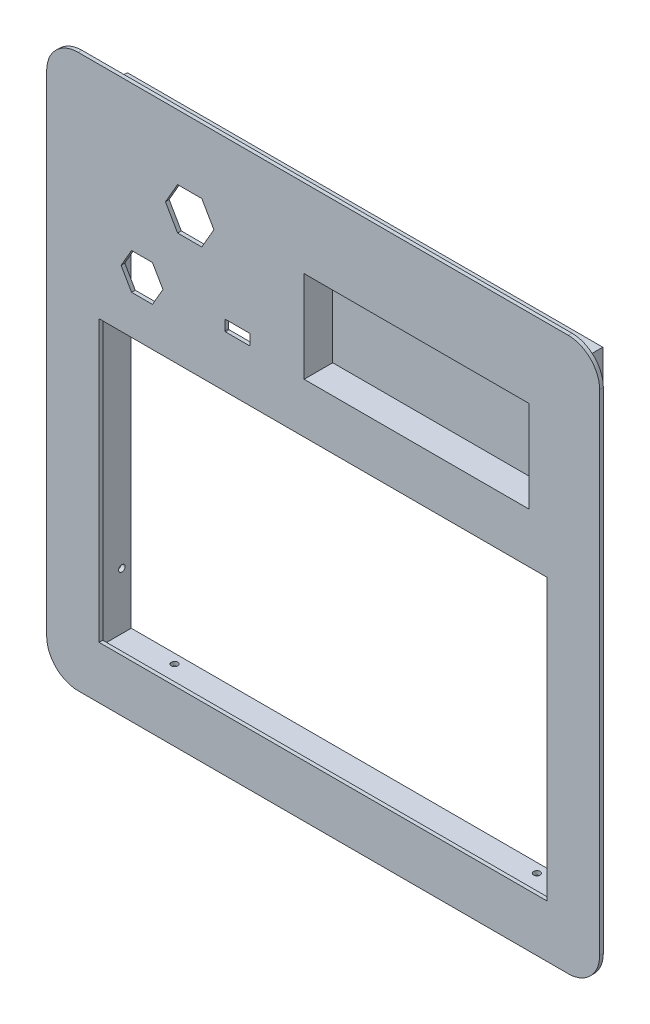
SolidWorks part; units mm, degrees
ref_plane "Front Plane" through (0, 0, 0) normal (0, 0, 1) x (1, 0, 0)
ref_plane "Top Plane" through (0, 0, 0) normal (0, 1, 0) x (1, 0, 0)
ref_plane "Right Plane" through (0, 0, 0) normal (1, 0, 0) x (0, 0, -1)
sketch "Sketch3" plane through (0, 0, 0) normal (0, 0, 1) x (1, 0, 0)
  line L0 (-117.5, 29.5) -> (117.5, 29.5)
  line L1 (-117.5, 29.5) -> (-117.5, -117.5)
  line L2 (-117.5, -117.5) -> (117.5, -117.5)
  line L3 (117.5, 29.5) -> (117.5, -117.5)
  line L8 (-38.77, 62.35) -> (-51.23, 62.35)
  line L9 (-51.54, 62.04) -> (-51.54, 56.96)
  line L10 (-51.23, 56.65) -> (-38.77, 56.65)
  line L11 (-38.46, 56.96) -> (-38.46, 62.04)
  line L12 (-12, 105.75) -> (110, 105.75)
  line L13 (-128.49, -145) -> (128.49, -145)
  line L14 (-145, -128.49) -> (-145, 128.49)
  line L15 (-128.49, 145) -> (128.49, 145)
  line L16 (145, -128.49) -> (145, 128.49)
  line L29 (-12, 105.75) -> (-12, 53.75)
  line L30 (-12, 53.75) -> (110, 53.75)
  line L31 (110, 105.75) -> (110, 53.75)
  line L32 (-70, 100) -> (-70, 59.5) construction
  line L33 (-57.2983, 100) -> (-63.6491, 111)
  line L34 (-84.0303, 59.5) -> (-89.5152, 69)
  line L35 (-89.5152, 69) -> (-100.4848, 69)
  line L36 (-100.4848, 69) -> (-105.9697, 59.5)
  line L37 (-105.9697, 59.5) -> (-100.4848, 50)
  line L38 (-100.4848, 50) -> (-89.5152, 50)
  line L39 (-89.5152, 50) -> (-84.0303, 59.5)
  line L40 (-63.6491, 111) -> (-76.3509, 111)
  line L41 (-76.3509, 111) -> (-82.7017, 100)
  line L42 (-82.7017, 100) -> (-76.3509, 89)
  line L43 (-76.3509, 89) -> (-63.6491, 89)
  line L44 (-63.6491, 89) -> (-57.2983, 100)
  arc A0 (-38.77, 56.65) -> (-38.46, 56.96) centre (-38.77, 56.96) ccw
  arc A1 (-51.54, 56.96) -> (-51.23, 56.65) centre (-51.23, 56.96) ccw
  arc A2 (-38.77, 62.35) -> (-38.46, 62.04) centre (-38.77, 62.04) cw
  arc A3 (-51.23, 62.35) -> (-51.54, 62.04) centre (-51.23, 62.04) ccw
  arc A4 (128.49, -145) -> (145, -128.49) centre (128.49, -128.49) ccw
  arc A5 (-128.49, -145) -> (-145, -128.49) centre (-128.49, -128.49) cw
  arc A6 (128.49, 145) -> (145, 128.49) centre (128.49, 128.49) cw
  arc A7 (-145, 128.49) -> (-128.49, 145) centre (-128.49, 128.49) cw
  circle A10 centre (-95, 59.5) radius 9.5 construction
  circle A11 centre (-70, 100) radius 11 construction
  point P26 (-51.54, 59.5)
  point P30 (-70, 79.75)
  point P32 (-45, 62.35)
  point P44 (-12, 79.75)
  point P58 (145, 0)
  point P59 (0, 145)
  dimension "D5" = 0.31
  dimension "D6" = 16.51
  dimension "D10" = 22
  dimension "D25" = 19
  dimension "D7" = 25
  dimension "D1" = 235
  dimension "D2" = 147
  dimension "D3" = 12.46
  dimension "D4" = 5.08
  dimension "D8" = 27.5
  dimension "D9" = 27.5
  dimension "D11" = 45
  dimension "D12" = 50
  dimension "D13" = 25
  dimension "D17" = 122
  dimension "D18" = 52
  dimension "D20" = 35
  dimension "D21" = 290
  dimension "D22" = 290
  dimension "D26" = 30
extrude "Boss-Extrude1" add sketch "Sketch3" against normal blind 2 draft 2 contours L31 L12 L29 L30 | A7 L14 A5 L13 A4 L16 A6 L15 A3 L8 A2 L11 A0 L10 A1 L9 L44 L43 L42 L41 L40 L33 L39 L38 L37 L36 L35 L34 L0 L3 L2 L1 L12 L31 L30 L29 region at (49, 79.75, 0) region at (-137.2643, -137.2643, 0)
ref_plane "Plane1" through (0, 0, -22) normal (0, 0, -1) x (-1, 0, 0)
sketch "Sketch4" plane through (0, 0, -22) normal (0, 0, -1) x (-1, 0, 0)
  line L1 (-124.65, -126.65) -> (124.65, -126.65)
  line L2 (-124.65, -126.65) -> (-124.65, 126.65)
  line L3 (-124.65, 126.65) -> (124.65, 126.65)
  line L4 (124.65, -126.65) -> (124.65, 126.65)
  line L5 (-124.65, -126.65) -> (124.65, 126.65) construction
  line L6 (-124.65, 126.65) -> (124.65, -126.65) construction
  point P0 (0, 0)
  dimension "D1" = 249.3
  dimension "D2" = 253.3
extrude "Boss-Extrude2" add sketch "Sketch4" against normal blind 20 draft 2 draft outward yes
sketch "Sketch5" plane through (0, 0, -22) normal (0, 0, -1) x (-1, 0, 0)
  line L14 (-122.65, -124.65) -> (122.65, -124.65)
  line L15 (122.65, -124.65) -> (122.65, 124.65)
  line L16 (-122.65, 124.65) -> (-122.65, -124.65)
  line L17 (122.65, 124.65) -> (-122.65, 124.65)
  line L18 (-122.65, -124.65) -> (122.65, -124.65)
  line L19 (122.65, -124.65) -> (122.65, 124.65)
  line L20 (-122.65, 124.65) -> (-122.65, -124.65)
  line L21 (122.65, 124.65) -> (-122.65, 124.65)
  dimension "D1" = 2
extrude "Cut-Extrude1" cut sketch "Sketch5" against normal blind 20
extrude "Boss-Extrude3" add sketch "Sketch3<3>" against normal blind 17 contours L31 L12 L29 L30 region at (49, 79.75, 0)
sketch "Sketch3<3>" plane through (0, 0, 0) normal (0, 0, 1) x (1, 0, 0) same geometry as "Sketch3"
sketch "Sketch6" plane through (0, 0, 0) normal (0, 0, 1) x (1, 0, 0)
  line L8 (108, 103.75) -> (-10, 103.75)
  line L9 (108, 55.75) -> (108, 103.75)
  line L10 (-10, 55.75) -> (108, 55.75)
  line L11 (-10, 103.75) -> (-10, 55.75)
  line L12 (108, 103.75) -> (-10, 103.75)
  line L13 (108, 55.75) -> (108, 103.75)
  line L14 (-10, 55.75) -> (108, 55.75)
  line L15 (-10, 103.75) -> (-10, 55.75)
  dimension "D1" = 2
extrude "Cut-Extrude2" cut sketch "Sketch6" against normal blind 15
fillet "Fillet1" radius 2 16 edges at (49, 105.75, -17) (49, 105.75, -2) (-12, 79.75, -17) (-12, 105.75, -9.5) (-12, 79.75, -2) (49, 53.75, -17) (-12, 53.75, -9.5) (49, 53.75, -2) (110, 105.75, -9.5) (110, 79.75, -17) (110, 53.75, -9.5) (110, 79.75, -2) (0, -124.65, -2) (-122.65, 0, -2) (122.65, 0, -2) (0, 124.65, -2)
sketch "Sketch11" plane through (0, -127.2631, -4.4441) normal (0, -0.9994, -0.0349) x (1, 0, 0)
  line L1 (0, 31.582) -> (0, -10.6236) construction
  line L3 (120.65, 2.2816) -> (-120.65, 2.2816) construction
  circle A0 centre (-95, -12.7184) radius 1.7
  circle A2 centre (95, -12.7184) radius 1.7
  point P2 (0, 0)
  point P9 (0, 0)
  dimension "D2" = 3.4
  dimension "D3" = 15
  dimension "D1" = 95
extrude "Cut-Extrude7" cut sketch "Sketch11" against normal blind 3 and the other way through all
mirror "Mirror1" about plane through (0, 0, 0) normal (0, 1, 0) of "Cut-Extrude7"
sketch "Sketch12" plane through (125.2655, 0, -4.3744) normal (0.9994, 0, -0.0349) x (-0.0349, 0, -0.9994)
  line L1 (-3.0592, -128.49) -> (-3.0592, 128.49) construction
  line L2 (-14.9596, 0) -> (22.657, 0) construction
  line L3 (-2.2131, 122.7198) -> (-2.2131, -122.7198) construction
  circle A0 centre (12.7869, 95) radius 1.7
  circle A1 centre (12.7869, -95) radius 1.7
  point P4 (-3.0592, 0)
  dimension "D1" = 3.4
  dimension "D2" = 15
  dimension "D3" = 95
extrude "Cut-Extrude8" cut sketch "Sketch12" against normal blind 3
mirror "Mirror2" about plane through (0, 0, 0) normal (1, 0, 0) of "Cut-Extrude8"
